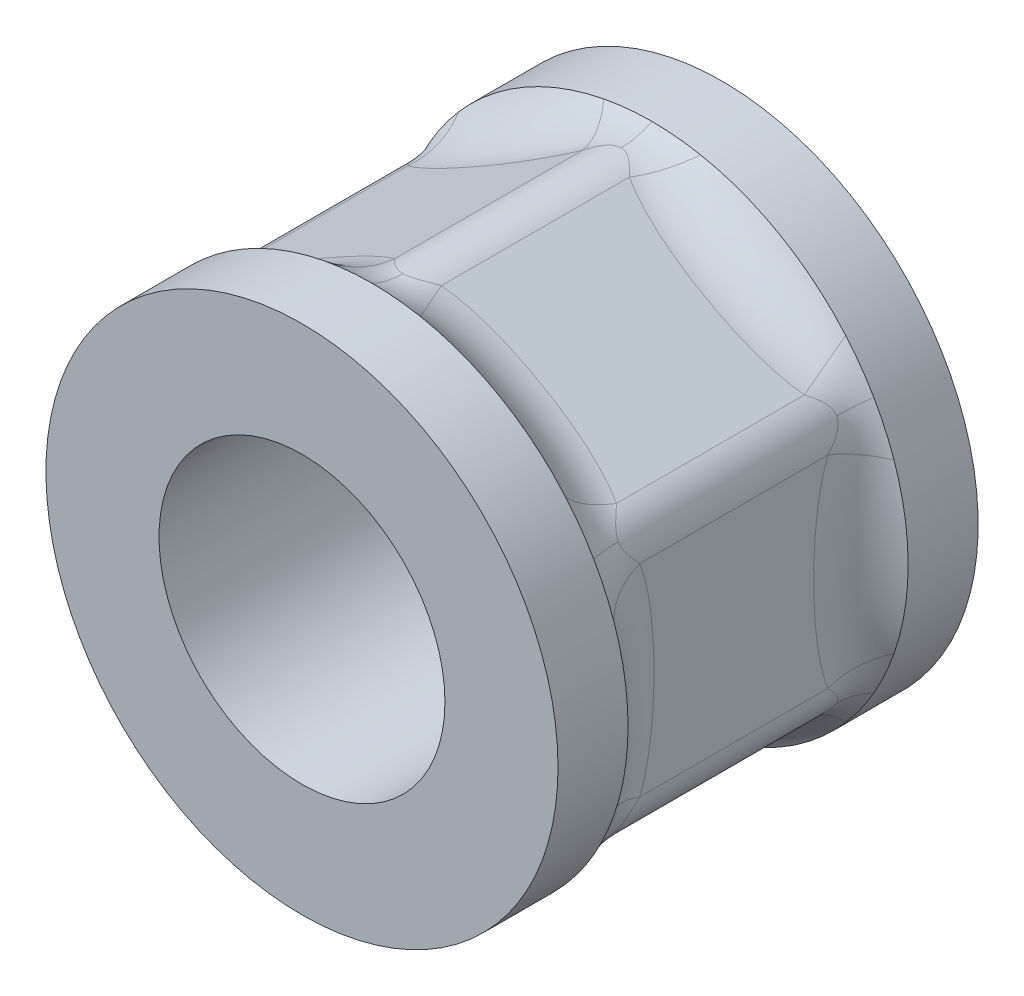
SolidWorks part; units mm, degrees
ref_plane "Front Plane" through (0, 0, 0) normal (0, 0, 1) x (1, 0, 0)
ref_plane "Top Plane" through (0, 0, 0) normal (0, 1, 0) x (1, 0, 0)
ref_plane "Right Plane" through (0, 0, 0) normal (1, 0, 0) x (0, 0, -1)
sketch "Sketch1" plane through (0, 0, 0) normal (0, 0, 1) x (1, 0, 0)
  line L1 (0, -7.5633) -> (6.55, -3.7816)
  line L2 (6.55, -3.7816) -> (6.55, 3.7816)
  line L3 (6.55, 3.7816) -> (0, 7.5633)
  line L4 (0, 7.5633) -> (-6.55, 3.7816)
  line L5 (-6.55, 3.7816) -> (-6.55, -3.7816)
  line L6 (-6.55, -3.7816) -> (0, -7.5633)
  line L7 (0, -10.9697) -> (9.5, -5.4848) construction
  line L8 (9.5, -5.4848) -> (9.5, 5.4848) construction
  line L9 (9.5, 5.4848) -> (0, 10.9697) construction
  line L10 (0, 10.9697) -> (-9.5, 5.4848) construction
  line L11 (-9.5, 5.4848) -> (-9.5, -5.4848) construction
  line L12 (-9.5, -5.4848) -> (0, -10.9697) construction
  circle A0 centre (0, 0) radius 6.55 construction
  circle A1 centre (0, 0) radius 10.9697
  circle A2 centre (0, 0) radius 9.5 construction
  dimension "D1" = 13.1
  dimension "D2" = 19
extrude "Boss-Extrude1" add sketch "Sketch1" along normal blind 6.4
sketch "Sketch2" plane through (0, 0, 6.4) normal (0, 0, 1) x (1, 0, 0)
  circle A0 centre (0, 0) radius 6.125
  circle A2 centre (0, 0) radius 10.9697 construction
  circle A3 centre (0, 0) radius 10.9697
  dimension "D1" = 12.25
extrude "Boss-Extrude2" add sketch "Sketch2" along normal blind 10 contours A3 | A0
sketch "Sketch3" plane through (0, 0, 0) normal (0, 0, -1) x (-1, 0, 0)
  circle A0 centre (0, 0) radius 4
  circle A1 centre (0, 0) radius 10.9697 construction
  circle A2 centre (0, 0) radius 10.9697
  dimension "D1" = 8
extrude "Boss-Extrude3" add sketch "Sketch3" along normal blind 1.6
sketch "Sketch4" plane through (0, 0, 0) normal (0, 0, 1) x (1, 0, 0)
  circle A0 centre (0, 0) radius 4 construction
  circle A1 centre (0, 0) radius 4
extrude "Boss-Extrude4" add sketch "Sketch4" against normal blind 0.6
sketch "Sketch5" plane through (0, 0, 6.4) normal (0, 0, -1) x (-1, 0, 0)
  line L1 (9.5, 5.4848) -> (0, 10.9697)
  line L2 (0, 10.9697) -> (-9.5, 5.4848)
  line L3 (-9.5, 5.4848) -> (-9.5, -5.4848)
  line L4 (-9.5, -5.4848) -> (0, -10.9697)
  line L5 (0, -10.9697) -> (9.5, -5.4848)
  line L6 (9.5, -5.4848) -> (9.5, 5.4848)
  circle A0 centre (0, 0) radius 9.5 construction
  circle A1 centre (0, 0) radius 10.9697 construction
  circle A2 centre (0, 0) radius 10.9697
extrude "Cut-Extrude1" cut sketch "Sketch5" against normal blind 7 and the other way blind 5 contours L3 A2 | L2 A2 | L1 A2 | L5 A2 | L4 A2 | L6 A2 region at (-10.0914, 0, 6.4) region at (-5.0457, 8.7394, 6.4) region at (5.0457, 8.7394, 6.4) region at (-5.0457, -8.7394, 6.4) region at (10.0914, 0, 6.4) region at (5.0457, -8.7394, 6.4)
fillet "Fillet4" radius 2 6 edges at (9.5, 5.4848, 7.4) (9.5, -5.4848, 7.4) (0, -10.9697, 7.4) (0, 10.9697, 7.4) (-9.5, 5.4848, 7.4) (-9.5, -5.4848, 7.4)
fillet "Fillet5" radius 3 12 edges at (4.75, 8.2272, 13.4) (-4.75, 8.2272, 13.4) (-9.5, 0, 13.4) (-4.75, -8.2272, 13.4) (4.75, -8.2272, 13.4) (9.5, 0, 13.4) (-4.75, 8.2272, 1.4) (-9.5, 0, 1.4) (-4.75, -8.2272, 1.4) (4.75, -8.2272, 1.4) (9.5, 0, 1.4) (4.75, 8.2272, 1.4)
